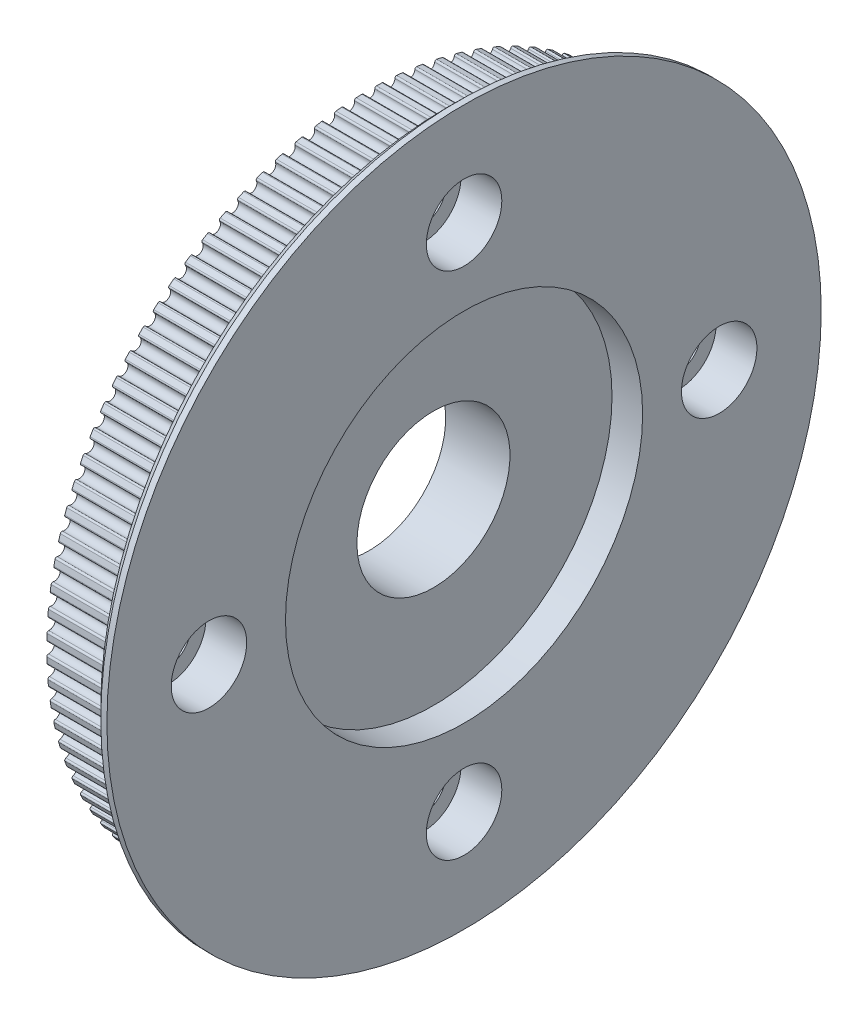
SolidWorks part; units mm, degrees
ref_plane "Front Plane" through (0, 0, 0) normal (0, 0, 1) x (1, 0, 0)
ref_plane "Top Plane" through (0, 0, 0) normal (0, 1, 0) x (1, 0, 0)
ref_plane "Right Plane" through (0, 0, 0) normal (1, 0, 0) x (0, 0, -1)
sketch "Sketch1" plane through (0, 0, 0) normal (1, 0, 0) x (0, 0, -1)
  circle A0 centre (0, 0) radius 31.6
  circle A1 centre (0, 0) radius 7.5
  dimension "D1" = 63.2
  dimension "D2" = 15
extrude "Boss-Extrude1" add sketch "Sketch1" along normal blind 7.7
sketch "Sketch2" plane through (0, 0, 0) normal (1, 0, 0) x (0, 0, -1)
  circle A0 centre (0, 0) radius 31.39 construction
  circle A1 centre (0, 31.39) radius 0.55
  circle A2 centre (0, 0) radius 31.39 construction
  circle A3 centre (1.971, 31.3281) radius 0.55
  circle A4 centre (0, 0) radius 31.39 construction
  circle A5 centre (3.9342, 31.1425) radius 0.55
  circle A6 centre (0, 0) radius 31.39 construction
  circle A7 centre (5.8819, 30.834) radius 0.55
  circle A8 centre (0, 0) radius 31.39 construction
  circle A9 centre (7.8064, 30.4038) radius 0.55
  circle A10 centre (0, 0) radius 31.39 construction
  circle A11 centre (9.7, 29.8537) radius 0.55
  circle A12 centre (0, 0) radius 31.39 construction
  circle A13 centre (11.5554, 29.1857) radius 0.55
  circle A14 centre (0, 0) radius 31.39 construction
  circle A15 centre (13.3652, 28.4025) radius 0.55
  circle A16 centre (0, 0) radius 31.39 construction
  circle A17 centre (15.1222, 27.5073) radius 0.55
  circle A18 centre (0, 0) radius 31.39 construction
  circle A19 centre (16.8196, 26.5035) radius 0.55
  circle A20 centre (0, 0) radius 31.39 construction
  circle A21 centre (18.4506, 25.395) radius 0.55
  circle A22 centre (0, 0) radius 31.39 construction
  circle A23 centre (20.0087, 24.1864) radius 0.55
  circle A24 centre (0, 0) radius 31.39 construction
  circle A25 centre (21.4879, 22.8823) radius 0.55
  circle A26 centre (0, 0) radius 31.39 construction
  circle A27 centre (22.8823, 21.4879) radius 0.55
  circle A28 centre (0, 0) radius 31.39 construction
  circle A29 centre (24.1864, 20.0087) radius 0.55
  circle A30 centre (0, 0) radius 31.39 construction
  circle A31 centre (25.395, 18.4506) radius 0.55
  circle A32 centre (0, 0) radius 31.39 construction
  circle A33 centre (26.5035, 16.8196) radius 0.55
  circle A34 centre (0, 0) radius 31.39 construction
  circle A35 centre (27.5073, 15.1222) radius 0.55
  circle A36 centre (0, 0) radius 31.39 construction
  circle A37 centre (28.4025, 13.3652) radius 0.55
  circle A38 centre (0, 0) radius 31.39 construction
  circle A39 centre (29.1857, 11.5554) radius 0.55
  circle A40 centre (0, 0) radius 31.39 construction
  circle A41 centre (29.8537, 9.7) radius 0.55
  circle A42 centre (0, 0) radius 31.39 construction
  circle A43 centre (30.4038, 7.8064) radius 0.55
  circle A44 centre (0, 0) radius 31.39 construction
  circle A45 centre (30.834, 5.8819) radius 0.55
  circle A46 centre (0, 0) radius 31.39 construction
  circle A47 centre (31.1425, 3.9342) radius 0.55
  circle A48 centre (0, 0) radius 31.39 construction
  circle A49 centre (31.3281, 1.971) radius 0.55
  circle A50 centre (0, 0) radius 31.39 construction
  circle A51 centre (31.39, 0) radius 0.55
  circle A52 centre (0, 0) radius 31.39 construction
  circle A53 centre (31.3281, -1.971) radius 0.55
  circle A54 centre (0, 0) radius 31.39 construction
  circle A55 centre (31.1425, -3.9342) radius 0.55
  circle A56 centre (0, 0) radius 31.39 construction
  circle A57 centre (30.834, -5.8819) radius 0.55
  circle A58 centre (0, 0) radius 31.39 construction
  circle A59 centre (30.4038, -7.8064) radius 0.55
  circle A60 centre (0, 0) radius 31.39 construction
  circle A61 centre (29.8537, -9.7) radius 0.55
  circle A62 centre (0, 0) radius 31.39 construction
  circle A63 centre (29.1857, -11.5554) radius 0.55
  circle A64 centre (0, 0) radius 31.39 construction
  circle A65 centre (28.4025, -13.3652) radius 0.55
  circle A66 centre (0, 0) radius 31.39 construction
  circle A67 centre (27.5073, -15.1222) radius 0.55
  circle A68 centre (0, 0) radius 31.39 construction
  circle A69 centre (26.5035, -16.8196) radius 0.55
  circle A70 centre (0, 0) radius 31.39 construction
  circle A71 centre (25.395, -18.4506) radius 0.55
  circle A72 centre (0, 0) radius 31.39 construction
  circle A73 centre (24.1864, -20.0087) radius 0.55
  circle A74 centre (0, 0) radius 31.39 construction
  circle A75 centre (22.8823, -21.4879) radius 0.55
  circle A76 centre (0, 0) radius 31.39 construction
  circle A77 centre (21.4879, -22.8823) radius 0.55
  circle A78 centre (0, 0) radius 31.39 construction
  circle A79 centre (20.0087, -24.1864) radius 0.55
  circle A80 centre (0, 0) radius 31.39 construction
  circle A81 centre (18.4506, -25.395) radius 0.55
  circle A82 centre (0, 0) radius 31.39 construction
  circle A83 centre (16.8196, -26.5035) radius 0.55
  circle A84 centre (0, 0) radius 31.39 construction
  circle A85 centre (15.1222, -27.5073) radius 0.55
  circle A86 centre (0, 0) radius 31.39 construction
  circle A87 centre (13.3652, -28.4025) radius 0.55
  circle A88 centre (0, 0) radius 31.39 construction
  circle A89 centre (11.5554, -29.1857) radius 0.55
  circle A90 centre (0, 0) radius 31.39 construction
  circle A91 centre (9.7, -29.8537) radius 0.55
  circle A92 centre (0, 0) radius 31.39 construction
  circle A93 centre (7.8064, -30.4038) radius 0.55
  circle A94 centre (0, 0) radius 31.39 construction
  circle A95 centre (5.8819, -30.834) radius 0.55
  circle A96 centre (0, 0) radius 31.39 construction
  circle A97 centre (3.9342, -31.1425) radius 0.55
  circle A98 centre (0, 0) radius 31.39 construction
  circle A99 centre (1.971, -31.3281) radius 0.55
  circle A100 centre (0, 0) radius 31.39 construction
  circle A101 centre (0, -31.39) radius 0.55
  circle A102 centre (0, 0) radius 31.39 construction
  circle A103 centre (-1.971, -31.3281) radius 0.55
  circle A104 centre (0, 0) radius 31.39 construction
  circle A105 centre (-3.9342, -31.1425) radius 0.55
  circle A106 centre (0, 0) radius 31.39 construction
  circle A107 centre (-5.8819, -30.834) radius 0.55
  circle A108 centre (0, 0) radius 31.39 construction
  circle A109 centre (-7.8064, -30.4038) radius 0.55
  circle A110 centre (0, 0) radius 31.39 construction
  circle A111 centre (-9.7, -29.8537) radius 0.55
  circle A112 centre (0, 0) radius 31.39 construction
  circle A113 centre (-11.5554, -29.1857) radius 0.55
  circle A114 centre (0, 0) radius 31.39 construction
  circle A115 centre (-13.3652, -28.4025) radius 0.55
  circle A116 centre (0, 0) radius 31.39 construction
  circle A117 centre (-15.1222, -27.5073) radius 0.55
  circle A118 centre (0, 0) radius 31.39 construction
  circle A119 centre (-16.8196, -26.5035) radius 0.55
  circle A120 centre (0, 0) radius 31.39 construction
  circle A121 centre (-18.4506, -25.395) radius 0.55
  circle A122 centre (0, 0) radius 31.39 construction
  circle A123 centre (-20.0087, -24.1864) radius 0.55
  circle A124 centre (0, 0) radius 31.39 construction
  circle A125 centre (-21.4879, -22.8823) radius 0.55
  circle A126 centre (0, 0) radius 31.39 construction
  circle A127 centre (-22.8823, -21.4879) radius 0.55
  circle A128 centre (0, 0) radius 31.39 construction
  circle A129 centre (-24.1864, -20.0087) radius 0.55
  circle A130 centre (0, 0) radius 31.39 construction
  circle A131 centre (-25.395, -18.4506) radius 0.55
  circle A132 centre (0, 0) radius 31.39 construction
  circle A133 centre (-26.5035, -16.8196) radius 0.55
  circle A134 centre (0, 0) radius 31.39 construction
  circle A135 centre (-27.5073, -15.1222) radius 0.55
  circle A136 centre (0, 0) radius 31.39 construction
  circle A137 centre (-28.4025, -13.3652) radius 0.55
  circle A138 centre (0, 0) radius 31.39 construction
  circle A139 centre (-29.1857, -11.5554) radius 0.55
  circle A140 centre (0, 0) radius 31.39 construction
  circle A141 centre (-29.8537, -9.7) radius 0.55
  circle A142 centre (0, 0) radius 31.39 construction
  circle A143 centre (-30.4038, -7.8064) radius 0.55
  circle A144 centre (0, 0) radius 31.39 construction
  circle A145 centre (-30.834, -5.8819) radius 0.55
  circle A146 centre (0, 0) radius 31.39 construction
  circle A147 centre (-31.1425, -3.9342) radius 0.55
  circle A148 centre (0, 0) radius 31.39 construction
  circle A149 centre (-31.3281, -1.971) radius 0.55
  circle A150 centre (0, 0) radius 31.39 construction
  circle A151 centre (-31.39, 0) radius 0.55
  circle A152 centre (0, 0) radius 31.39 construction
  circle A153 centre (-31.3281, 1.971) radius 0.55
  circle A154 centre (0, 0) radius 31.39 construction
  circle A155 centre (-31.1425, 3.9342) radius 0.55
  circle A156 centre (0, 0) radius 31.39 construction
  circle A157 centre (-30.834, 5.8819) radius 0.55
  circle A158 centre (0, 0) radius 31.39 construction
  circle A159 centre (-30.4038, 7.8064) radius 0.55
  circle A160 centre (0, 0) radius 31.39 construction
  circle A161 centre (-29.8537, 9.7) radius 0.55
  circle A162 centre (0, 0) radius 31.39 construction
  circle A163 centre (-29.1857, 11.5554) radius 0.55
  circle A164 centre (0, 0) radius 31.39 construction
  circle A165 centre (-28.4025, 13.3652) radius 0.55
  circle A166 centre (0, 0) radius 31.39 construction
  circle A167 centre (-27.5073, 15.1222) radius 0.55
  circle A168 centre (0, 0) radius 31.39 construction
  circle A169 centre (-26.5035, 16.8196) radius 0.55
  circle A170 centre (0, 0) radius 31.39 construction
  circle A171 centre (-25.395, 18.4506) radius 0.55
  circle A172 centre (0, 0) radius 31.39 construction
  circle A173 centre (-24.1864, 20.0087) radius 0.55
  circle A174 centre (0, 0) radius 31.39 construction
  circle A175 centre (-22.8823, 21.4879) radius 0.55
  circle A176 centre (0, 0) radius 31.39 construction
  circle A177 centre (-21.4879, 22.8823) radius 0.55
  circle A178 centre (0, 0) radius 31.39 construction
  circle A179 centre (-20.0087, 24.1864) radius 0.55
  circle A180 centre (0, 0) radius 31.39 construction
  circle A181 centre (-18.4506, 25.395) radius 0.55
  circle A182 centre (0, 0) radius 31.39 construction
  circle A183 centre (-16.8196, 26.5035) radius 0.55
  circle A184 centre (0, 0) radius 31.39 construction
  circle A185 centre (-15.1222, 27.5073) radius 0.55
  circle A186 centre (0, 0) radius 31.39 construction
  circle A187 centre (-13.3652, 28.4025) radius 0.55
  circle A188 centre (0, 0) radius 31.39 construction
  circle A189 centre (-11.5554, 29.1857) radius 0.55
  circle A190 centre (0, 0) radius 31.39 construction
  circle A191 centre (-9.7, 29.8537) radius 0.55
  circle A192 centre (0, 0) radius 31.39 construction
  circle A193 centre (-7.8064, 30.4038) radius 0.55
  circle A194 centre (0, 0) radius 31.39 construction
  circle A195 centre (-5.8819, 30.834) radius 0.55
  circle A196 centre (0, 0) radius 31.39 construction
  circle A197 centre (-3.9342, 31.1425) radius 0.55
  circle A198 centre (0, 0) radius 31.39 construction
  circle A199 centre (-1.971, 31.3281) radius 0.55
  point P305 (0, 0)
  dimension "D1" = 62.78
  dimension "D2" = 1.1
  dimension "D3" = 100
extrude "Cut-Extrude1" cut sketch "Sketch2" along normal up to surface (7.7 mm away) up to face at (7.7, 0, -31.6)
fillet "Fillet1" radius 0.16 200 edges at (3.85, 31.5959, 0.51) (3.85, 31.5656, 1.4749) (3.85, 21.2571, -23.3815) (3.85, 22.6833, -22.0007) (3.85, 22.0007, -22.6833) (3.85, 20.5329, -24.02) (3.85, 19.747, -24.6701) (3.85, 18.9842, -25.2618) (3.85, 18.159, -25.8614) (3.85, 17.3605, -26.404) (3.85, 16.4993, -26.9506) (3.85, 15.6684, -27.442) (3.85, 14.7745, -27.9334) (3.85, 13.9143, -28.3717) (3.85, 12.9914, -28.806) (3.85, 12.1054, -29.1894) (3.85, 23.3815, -21.2571) (3.85, 24.02, -20.5329) (3.85, 24.6701, -19.747) (3.85, 25.2618, -18.9842) (3.85, 25.8614, -18.159) (3.85, 26.404, -17.3605) (3.85, 26.9506, -16.4993) (3.85, 27.442, -15.6684) (3.85, 27.9334, -14.7745) (3.85, 28.3717, -13.9143) (3.85, 28.806, -12.9914) (3.85, 29.1894, -12.1054) (3.85, 29.5649, -11.157) (3.85, 29.8919, -10.2487) (3.85, 30.2071, -9.2786) (3.85, 30.4764, -8.3516) (3.85, 30.7301, -7.3636) (3.85, 30.9407, -6.4215) (3.85, 31.1318, -5.4195) (3.85, 31.2828, -4.466) (3.85, 31.4107, -3.454) (3.85, 31.5015, -2.4929) (3.85, 31.5656, -1.4749) (3.85, 31.5959, -0.51) (3.85, 31.5015, 2.4929) (3.85, 31.4107, 3.454) (3.85, 31.2828, 4.466) (3.85, 31.1318, 5.4195) (3.85, 30.9407, 6.4215) (3.85, 30.7301, 7.3636) (3.85, 30.4764, 8.3516) (3.85, 30.2071, 9.2786) (3.85, 29.8919, 10.2487) (3.85, 29.5649, 11.157) (3.85, 29.1894, 12.1054) (3.85, 28.806, 12.9914) (3.85, 28.3717, 13.9143) (3.85, 27.9334, 14.7745) (3.85, 27.442, 15.6684) (3.85, 26.9506, 16.4993) (3.85, 26.404, 17.3605) (3.85, 25.8614, 18.159) (3.85, 25.2618, 18.9842) (3.85, 24.6701, 19.747) (3.85, 24.02, 20.5329) (3.85, 23.3815, 21.2571) (3.85, 22.6833, 22.0007) (3.85, 22.0007, 22.6833) (3.85, 21.2571, 23.3815) (3.85, 20.5329, 24.02) (3.85, 19.747, 24.6701) (3.85, 18.9842, 25.2618) (3.85, 18.159, 25.8614) (3.85, 17.3605, 26.404) (3.85, 16.4993, 26.9506) (3.85, 15.6684, 27.442) (3.85, 14.7745, 27.9334) (3.85, 13.9143, 28.3717) (3.85, 12.9914, 28.806) (3.85, 12.1054, 29.1894) (3.85, 11.157, 29.5649) (3.85, 10.2487, 29.8919) (3.85, 9.2786, 30.2071) (3.85, 8.3516, 30.4764) (3.85, 7.3636, 30.7301) (3.85, 6.4215, 30.9407) (3.85, 5.4195, 31.1318) (3.85, 4.466, 31.2828) (3.85, 3.454, 31.4107) (3.85, 2.4929, 31.5015) (3.85, 1.4749, 31.5656) (3.85, 0.51, 31.5959) (3.85, -0.51, 31.5959) (3.85, -1.4749, 31.5656) (3.85, -2.4929, 31.5015) (3.85, -3.454, 31.4107) (3.85, -4.466, 31.2828) (3.85, -5.4195, 31.1318) (3.85, -6.4215, 30.9407) (3.85, -7.3636, 30.7301) (3.85, -8.3516, 30.4764) (3.85, -9.2786, 30.2071) (3.85, -10.2487, 29.8919) (3.85, -11.157, 29.5649) (3.85, -12.1054, 29.1894) (3.85, -12.9914, 28.806) (3.85, -13.9143, 28.3717) (3.85, -14.7745, 27.9334) (3.85, -15.6684, 27.442) (3.85, -16.4993, 26.9506) (3.85, -17.3605, 26.404) (3.85, -18.159, 25.8614) (3.85, -18.9842, 25.2618) (3.85, -19.747, 24.6701) (3.85, -20.5329, 24.02) (3.85, -21.2571, 23.3815) (3.85, -22.0007, 22.6833) (3.85, -22.6833, 22.0007) (3.85, -23.3815, 21.2571) (3.85, -24.02, 20.5329) (3.85, -24.6701, 19.747) (3.85, -25.2618, 18.9842) (3.85, -25.8614, 18.159) (3.85, -26.404, 17.3605) (3.85, -26.9506, 16.4993) (3.85, -27.442, 15.6684) (3.85, -27.9334, 14.7745) (3.85, -28.3717, 13.9143) (3.85, -28.806, 12.9914) (3.85, -29.1894, 12.1054) (3.85, -29.5649, 11.157) (3.85, -29.8919, 10.2487) (3.85, -30.2071, 9.2786) (3.85, -30.4764, 8.3516) (3.85, -30.7301, 7.3636) (3.85, -30.9407, 6.4215) (3.85, -31.1318, 5.4195) (3.85, -31.2828, 4.466) (3.85, -31.4107, 3.454) (3.85, -31.5015, 2.4929) (3.85, -31.5656, 1.4749) (3.85, -31.5959, 0.51) (3.85, -31.5959, -0.51) (3.85, -31.5656, -1.4749) (3.85, -31.5015, -2.4929) (3.85, -31.4107, -3.454) (3.85, -31.2828, -4.466) (3.85, -31.1318, -5.4195) (3.85, -30.9407, -6.4215) (3.85, -30.7301, -7.3636) (3.85, -30.4764, -8.3516) (3.85, -30.2071, -9.2786) (3.85, -29.8919, -10.2487) (3.85, -29.5649, -11.157) (3.85, -29.1894, -12.1054) (3.85, -28.806, -12.9914) (3.85, -28.3717, -13.9143) (3.85, -27.9334, -14.7745) (3.85, -27.442, -15.6684) (3.85, -26.9506, -16.4993) (3.85, -26.404, -17.3605) (3.85, -25.8614, -18.159) (3.85, -25.2618, -18.9842) (3.85, -24.6701, -19.747) (3.85, -24.02, -20.5329) (3.85, -23.3815, -21.2571) (3.85, -22.6833, -22.0007) (3.85, -22.0007, -22.6833) (3.85, -21.2571, -23.3815) (3.85, -20.5329, -24.02) (3.85, -19.747, -24.6701) (3.85, -18.9842, -25.2618) (3.85, -18.159, -25.8614) (3.85, -17.3605, -26.404) (3.85, -16.4993, -26.9506) (3.85, -15.6684, -27.442) (3.85, -14.7745, -27.9334) (3.85, -13.9143, -28.3717) (3.85, -12.9914, -28.806) (3.85, -12.1054, -29.1894) (3.85, -11.157, -29.5649) (3.85, -10.2487, -29.8919) (3.85, -9.2786, -30.2071) (3.85, -8.3516, -30.4764) (3.85, -7.3636, -30.7301) (3.85, -6.4215, -30.9407) (3.85, -5.4195, -31.1318) (3.85, -4.466, -31.2828) (3.85, -3.454, -31.4107) (3.85, -2.4929, -31.5015) (3.85, 11.157, -29.5649) (3.85, 10.2487, -29.8919) (3.85, 9.2786, -30.2071) (3.85, 8.3516, -30.4764) (3.85, 7.3636, -30.7301) (3.85, 6.4215, -30.9407) (3.85, 5.4195, -31.1318) (3.85, 4.466, -31.2828) (3.85, 3.454, -31.4107) (3.85, 2.4929, -31.5015) (3.85, 1.4749, -31.5656) (3.85, 0.51, -31.5959) (3.85, -1.4749, -31.5656) (3.85, -0.51, -31.5959)
ref_axis "Axis1" through (7.7, 0, 0) along (-1, 0, 0)
sketch "Sketch3" plane through (7.7, 0, 0) normal (1, 0, 0) x (0, 0, -1)
  circle A0 centre (0, 0) radius 35
  circle A1 centre (0, 0) radius 7.5
  circle A2 centre (0, 0) radius 7.5 construction
  dimension "D1" = 70
extrude "Boss-Extrude2" add sketch "Sketch3" along normal blind 1.6
sketch "Sketch6" plane through (9.3, 0, 0) normal (1, 0, 0) x (0, 0, -1)
  circle A0 centre (0, -25) radius 2.2
  circle A3 centre (-25, 0) radius 2.2
  circle A4 centre (0, 25) radius 2.2
  circle A5 centre (25, 0) radius 2.2
  point P13 (0, 0)
  dimension "D1" = 4.4
  dimension "D2" = 25
  dimension "D3" = 4
extrude "Cut-Extrude6" cut sketch "Sketch6" against normal up to surface (9.3 mm away) up to face at (0, 0, 0)
sketch "Sketch7" plane through (9.3, 0, 0) normal (1, 0, 0) x (0, 0, -1)
  circle A0 centre (0, -25) radius 3.7
  circle A1 centre (-25, 0) radius 3.7
  circle A2 centre (0, 25) radius 3.7
  circle A3 centre (25, 0) radius 3.7
  point P12 (0, 0)
  dimension "D1" = 7.4
  dimension "D2" = 4
extrude "Cut-Extrude4" cut sketch "Sketch7" against normal blind 4
chamfer "Chamfer1" distance 1 angle 45 1 edges at (7.7, 0, -35)
sketch "Sketch8" plane through (9.3, 0, 0) normal (1, 0, 0) x (0, 0, -1)
  circle A0 centre (0, 0) radius 17.5
  dimension "D1" = 35
extrude "Cut-Extrude7" cut sketch "Sketch8" against normal blind 3
